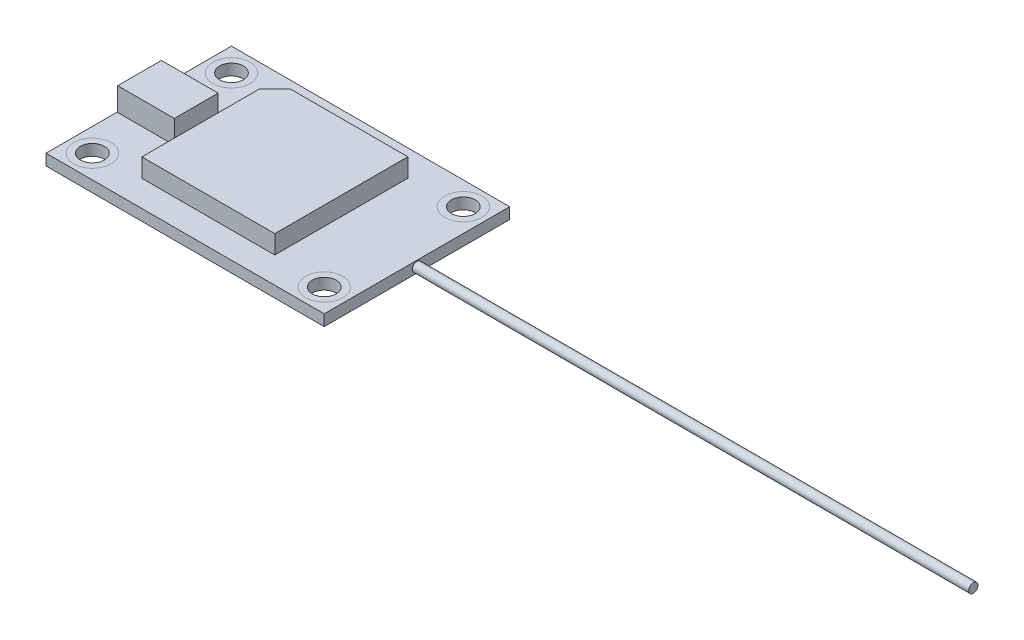
SolidWorks part; units mm, degrees
ref_plane "Front Plane" through (0, 0, 0) normal (0, 0, 1) x (1, 0, 0)
ref_plane "Top Plane" through (0, 0, 0) normal (0, 1, 0) x (1, 0, 0)
ref_plane "Right Plane" through (0, 0, 0) normal (1, 0, 0) x (0, 0, -1)
sketch "Sketch1" plane through (0, 0, 0) normal (0, 1, 0) x (1, 0, 0)
  line L1 (19.05, -12.7) -> (-19.05, -12.7)
  line L2 (19.05, -12.7) -> (19.05, 12.7)
  line L3 (19.05, 12.7) -> (-19.05, 12.7)
  line L4 (-19.05, -12.7) -> (-19.05, 12.7)
  line L5 (19.05, -12.7) -> (-19.05, 12.7) construction
  line L6 (19.05, 12.7) -> (-19.05, -12.7) construction
  point P0 (0, 0)
  dimension "D1" = 25.4
  dimension "D2" = 38.1
extrude "Boss-Extrude1" add sketch "Sketch1" along normal blind 1.524
sketch "Sketch2" plane through (0, 1.524, 0) normal (0, 1, 0) x (1, 0, 0)
  line L0 (-1.3341, -12.7013) -> (-1.4066, 12.6986) construction
  line L1 (19.05, 12.7) -> (-19.05, 12.7) construction
  line L2 (15.875, -9.525) -> (-15.875, -9.525)
  line L3 (15.875, -9.525) -> (15.875, 9.525)
  line L4 (15.875, 9.525) -> (-15.875, 9.525)
  line L5 (-15.875, -9.525) -> (-15.875, 9.525)
  line L6 (15.875, -9.525) -> (-15.875, 9.525) construction
  line L7 (15.875, 9.525) -> (-15.875, -9.525) construction
  line L8 (-19.05, 12.7) -> (-19.05, -12.7) construction
  line L9 (-9.5081, -9.1127) -> (8.6955, -9.1127)
  line L10 (8.6955, -9.1127) -> (8.6955, 9.1048)
  line L11 (8.6955, 9.1048) -> (-7.3977, 9.1048)
  line L12 (-7.3977, 9.1048) -> (-9.5081, 6.9944)
  line L13 (-9.5081, 6.9944) -> (-9.5081, -9.1127)
  line L14 (-18.9728, 3.0318) -> (-11.2131, 3.0318)
  line L15 (-11.2131, 3.0318) -> (-11.2131, -2.9656)
  line L16 (-11.2131, -2.9656) -> (-18.9728, -2.9656)
  line L17 (-18.9728, -2.9656) -> (-18.9728, 3.0318)
  point P2 (0, 0)
  dimension "D1" = 25.4
  dimension "D2" = 3.175
  dimension "D3" = 3.175
hole_wizard "#4 Clearance Hole1" positions "Sketch3" profile "Sketch4" hole size "#4" standard "ANSI Inch" end condition through all
sketch "Sketch3" plane through (0, 1.524, 0) normal (0, 1, 0) x (1, 0, 0)
  point P0 (-15.875, 9.525)
  point P3 (15.875, 9.525)
  point P6 (15.875, -9.525)
  point P9 (-15.875, -9.525)
sketch "Sketch4" plane through (-15.875, 1.524, -9.525) normal (1, 0, 0) x (0, 0, 1)
  line L0 (0, 0) -> (0, 1.524)
  line L1 (0, 1.524) -> (1.6319, 1.524)
  line L2 (1.6319, 1.524) -> (1.6319, 0)
  line L5 (1.6319, 0) -> (0, 0)
  line L11 (0, -6.35) -> (0, 107.95) construction
  dimension "Thru Hole Dia." = 3.2639
  dimension "Thru Hole Depth" = 1.524
extrude "Boss-Extrude2" add sketch "Sketch2" along normal blind 2.54 contours L12 L13 L9 L10 L11
extrude "Boss-Extrude3" add sketch "Sketch2<3>" along normal blind 3.175 contours L17 L16 L5 L14 | L16 L15 L14 L5 region at (-17.4239, 1.524, -0.0331) region at (-13.5441, 1.524, -0.0331)
sketch "Sketch2<3>" plane through (0, 1.524, 0) normal (0, 1, 0) x (1, 0, 0) same geometry as "Sketch2"
sketch "Sketch5" plane through (0, 1.524, 0) normal (0, 1, 0) x (1, 0, 0)
  circle A0 centre (-15.875, 9.525) radius 2.54
  circle A1 centre (15.875, 9.525) radius 2.54
  circle A2 centre (15.875, -9.525) radius 2.54
  circle A3 centre (-15.875, -9.525) radius 2.54
  dimension "D1" = 5.08
split line "Split Line1"
sketch "Sketch6" plane through (19.05, 0, 0) normal (1, 0, 0) x (0, 0, -1)
  line L0 (12.7, 1.524) -> (12.7, 0) construction
  circle A0 centre (0, 0.762) radius 0.635
  point P7 (12.7, 0.762)
  dimension "D1" = 1.27
extrude "Boss-Extrude4" add sketch "Sketch6" along normal blind 76.2
